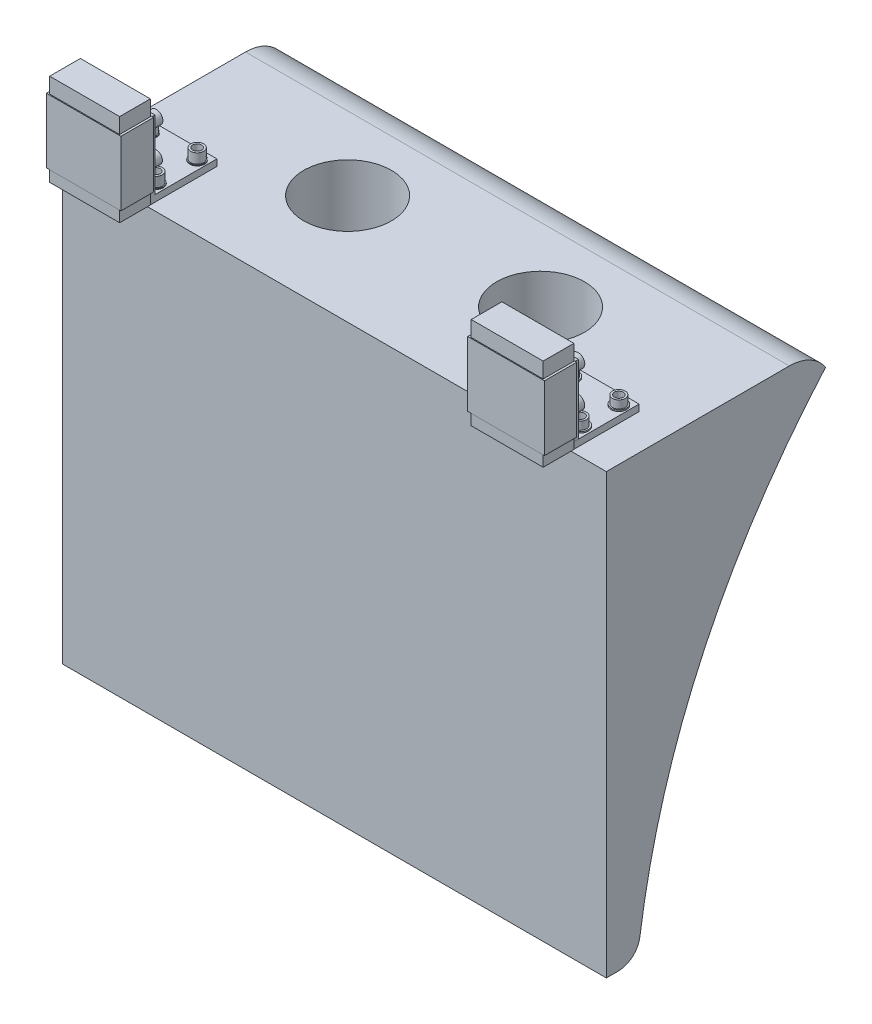
SolidWorks part; units mm, degrees
ref_plane "Front Plane" through (0, 0, 0) normal (0, 0, 1) x (1, 0, 0)
ref_plane "Top Plane" through (0, 0, 0) normal (0, 1, 0) x (1, 0, 0)
ref_plane "Right Plane" through (0, 0, 0) normal (1, 0, 0) x (0, 0, -1)
sketch "Sketch1" plane through (0, 0, 0) normal (1, 0, 0) x (0, 0, -1)
  line L0 (-139.1874, 113.9977) -> (-139.1874, -86.0023)
  line L1 (-139.1874, -86.0023) -> (-125.0344, -86.0023)
  line L4 (-39.1874, 113.9977) -> (-139.1874, 113.9977)
  line L5 (-39.1874, 113.9977) -> (-39.1874, 105.2432)
  spline S2 degree 2 poles (-125.0344, -86.0023) (-112.0669, 22.1606) (-39.1874, 105.2432) knots 0 0 0 1 1 1
  dimension "D1" = 200
  dimension "D2" = 100
extrude "Boss-Extrude1" add sketch "Sketch1" along normal blind 242 and the other way blind 6 contours L5 S2 L1 L0 L4
fillet "Fillet1" radius 10 1 edges at (118, -86.0023, 125.0344)
sketch "Sketch2" plane through (0, 113.9977, 0) normal (0, 1, 0) x (1, 0, 0)
  line L0 (242, -139.1874) -> (-6, -139.1874) construction
  line L1 (242, -39.1874) -> (242, -139.1874) construction
  line L2 (-6, -39.1874) -> (-6, -139.1874) construction
  circle A0 centre (162, -89.1874) radius 20
  circle A1 centre (44, -39.1874) radius 35
  point P10 (143, -89.1874)
  point P11 (0, 0)
  dimension "D5" = 70
  dimension "D6" = 40
  dimension "D1" = 50
  dimension "D2" = 80
  dimension "D3" = 50
  dimension "D4" = 100
extrude "Cut-Extrude2" cut sketch "Sketch2" against normal blind 30 contours A0
sketch "Sketch4" plane through (0, 113.9977, 0) normal (0, 1, 0) x (1, 0, 0)
  line L0 (-6, -39.1874) -> (-6, -139.1874) construction
  line L1 (242, -139.1874) -> (-6, -139.1874) construction
  circle A0 centre (74, -89.1874) radius 20
  dimension "D1" = 40
  dimension "D2" = 80
  dimension "D3" = 50
extrude "Cut-Extrude3" cut sketch "Sketch4" against normal blind 30
fillet "Fillet2" radius 20 1 edges at (118, 113.9977, 39.1874)
sketch "Sketch5" plane through (0, 113.9977, 0) normal (0, 1, 0) x (1, 0, 0)
  line L1 (287.0474, -139.0857) -> (257.0932, -139.0857)
  line L2 (287.0474, -139.0857) -> (287.0474, -108.0353)
  line L3 (287.0474, -108.0353) -> (257.0932, -108.0353)
  line L4 (257.0932, -139.0857) -> (257.0932, -108.0353)
  line L5 (3.1819, -139.2752) -> (32.6867, -139.2752)
  line L6 (3.1819, -139.2752) -> (3.1819, -107.4758)
  line L7 (3.1819, -107.4758) -> (32.6867, -107.4758)
  line L8 (32.6867, -139.2752) -> (32.6867, -107.4758)
extrude "Boss-Extrude2" add sketch "Sketch5" along normal blind 3
sketch "Sketch6" plane through (0, 116.9977, 0) normal (0, 1, 0) x (1, 0, 0)
  circle A0 centre (282.4766, -130.3755) radius 3.7166
  circle A1 centre (261.3092, -130.3442) radius 3.5214
  circle A2 centre (282.925, -113.1792) radius 3.4861
  circle A3 centre (261.0046, -113.1473) radius 3.5318
extrude "Boss-Extrude3" add sketch "Sketch6" along normal blind 0.6 contours A1 | A3 | A2 | A0 region at (261.3092, 116.9977, 130.3442) region at (282.925, 116.9977, 113.1792) region at (261.0046, 116.9977, 113.1473)
sketch "Sketch7" plane through (0, 117.5977, 0) normal (0, 1, 0) x (1, 0, 0)
  circle A0 centre (261.3092, -130.3442) radius 2.7903
  circle A1 centre (261.0046, -113.1473) radius 2.8891
  circle A2 centre (282.4766, -130.3755) radius 2.9455
  circle A3 centre (282.925, -113.1792) radius 2.9236
  circle A4 centre (282.925, -113.1792) radius 2.0236
  circle A5 centre (261.0046, -113.1473) radius 1.9891
  circle A6 centre (261.3092, -130.3442) radius 1.8903
  circle A7 centre (282.4766, -130.3755) radius 2.0455
  dimension "D1" = 0.9
extrude "Boss-Extrude4" add sketch "Sketch7" along normal blind 3.6
sketch "Sketch8" plane through (0, 116.9977, 0) normal (0, 1, 0) x (1, 0, 0)
  circle A0 centre (7.3677, -130.7754) radius 3.5903
  circle A1 centre (28.5717, -131.1234) radius 3.3212
  circle A2 centre (28.6202, -112.4161) radius 3.3684
  circle A3 centre (7.1046, -112.7317) radius 3.3146
extrude "Boss-Extrude5" add sketch "Sketch8" along normal blind 0.4 contours A0 | A3 | A2 | A1 region at (7.3677, 116.9977, 130.7754) region at (28.6202, 116.9977, 112.4161) region at (7.1046, 116.9977, 112.7317)
sketch "Sketch9" plane through (0, 117.3977, 0) normal (0, 1, 0) x (1, 0, 0)
  circle A0 centre (7.0954, -112.6967) radius 2.9562
  circle A1 centre (28.6202, -112.4161) radius 2.9528
  circle A2 centre (7.3677, -130.7754) radius 3.1751
  circle A3 centre (28.5717, -131.1234) radius 2.8914
  circle A4 centre (7.0954, -112.6967) radius 2.0562
  circle A5 centre (28.6202, -112.4161) radius 2.0528
  circle A6 centre (7.3677, -130.7754) radius 2.2751
  circle A7 centre (28.5717, -131.1234) radius 1.9914
  dimension "D1" = 0.9
extrude "Boss-Extrude6" add sketch "Sketch9" along normal blind 4.5
sketch "Sketch11" plane through (0, 116.9977, 0) normal (0, 1, 0) x (1, 0, 0)
  line L0 (287.0474, -139.0857) -> (287.0474, -108.0353) construction
  line L1 (287.0474, -135.7438) -> (257.0932, -135.7438)
  line L2 (287.0474, -135.7438) -> (287.0474, -139.0857)
  line L3 (287.0474, -139.0857) -> (257.0932, -139.0857)
  line L4 (257.0932, -135.7438) -> (257.0932, -139.0857)
  line L5 (32.6867, -139.2752) -> (32.6867, -107.4758) construction
  line L6 (32.6867, -135.7438) -> (3.1819, -135.7438)
  line L7 (32.6867, -135.7438) -> (32.6867, -139.2752)
  line L8 (32.6867, -139.2752) -> (3.1819, -139.2752)
  line L9 (3.1819, -135.7438) -> (3.1819, -139.2752)
extrude "Boss-Extrude7" add sketch "Sketch11" along normal blind 31.5
sketch "Sketch12" plane through (0, 0, 135.7438) normal (0, 0, -1) x (-1, 0, 0)
  circle A0 centre (-282.078, 143.2555) radius 3.5716
  circle A1 centre (-261.9163, 142.919) radius 3.63
  circle A2 centre (-281.9256, 126.8001) radius 3.5382
  circle A3 centre (-261.7812, 126.8367) radius 3.5128
extrude "Boss-Extrude8" add sketch "Sketch12" along normal blind 0.4
sketch "Sketch13" plane through (0, 0, 135.7438) normal (0, 0, -1) x (-1, 0, 0)
  circle A0 centre (-28.4144, 143.1344) radius 3.3554
  circle A1 centre (-28.4527, 127.3354) radius 3.1994
  circle A2 centre (-7.3975, 127.1758) radius 3.1344
  circle A3 centre (-7.6472, 142.9311) radius 3.4439
extrude "Boss-Extrude9" add sketch "Sketch13" along normal blind 0.4 contours A0 | A1 | A2 | A3 region at (28.4144, 143.1344, 135.7438) region at (28.4527, 127.3354, 135.7438) region at (7.3975, 127.1758, 135.7438)
sketch "Sketch14" plane through (0, 0, 135.3438) normal (0, 0, -1) x (-1, 0, 0)
  circle A0 centre (-282.078, 143.2555) radius 2.9987
  circle A1 centre (-261.873, 142.9358) radius 3.1841
  circle A2 centre (-261.7812, 126.8367) radius 2.9866
  circle A3 centre (-281.9256, 126.8001) radius 3.0844
  circle A4 centre (-28.44, 143.1429) radius 2.9722
  circle A5 centre (-7.6472, 142.9311) radius 2.9949
  circle A6 centre (-28.4527, 127.3354) radius 2.7475
  circle A7 centre (-7.3975, 127.1758) radius 2.743
  circle A8 centre (-28.44, 143.1429) radius 2.0722
  circle A9 centre (-7.6472, 142.9311) radius 2.0949
  circle A10 centre (-28.4527, 127.3354) radius 1.8475
  circle A11 centre (-7.3975, 127.1758) radius 1.843
  circle A12 centre (-282.078, 143.2555) radius 2.0987
  circle A13 centre (-261.873, 142.9358) radius 2.2841
  circle A14 centre (-281.9256, 126.8001) radius 2.1844
  circle A15 centre (-261.7812, 126.8367) radius 2.0866
  dimension "D1" = 0.9
extrude "Boss-Extrude10" add sketch "Sketch14" along normal blind 4.5
sketch "Sketch15" plane through (0, 0, 139.0857) normal (0, 0, 1) x (1, 0, 0)
  line L1 (255.5139, 157.1398) -> (288.336, 157.1398)
  line L2 (255.5139, 157.1398) -> (255.5139, 115.1906)
  line L3 (255.5139, 115.1906) -> (288.336, 115.1906)
  line L4 (288.336, 157.1398) -> (288.336, 115.1906)
  line L5 (2.0437, 157.1398) -> (33.9407, 157.1398)
  line L6 (2.0437, 157.1398) -> (2.0437, 115.1906)
  line L7 (2.0437, 115.1906) -> (33.9407, 115.1906)
  line L8 (33.9407, 157.1398) -> (33.9407, 115.1906)
extrude "Boss-Extrude11" add sketch "Sketch15" along normal blind 14
sketch "Sketch17" plane through (33.9407, 0, 0) normal (1, 0, 0) x (0, 0, -1)
  line L1 (-153.4979, 150.0543) -> (-138.5796, 150.0543)
  line L2 (-153.4979, 150.0543) -> (-153.4979, 120.5867)
  line L3 (-153.4979, 120.5867) -> (-138.5796, 120.5867)
  line L4 (-138.5796, 150.0543) -> (-138.5796, 120.5867)
extrude "Boss-Extrude12" add sketch "Sketch17" against normal blind 33 and the other way blind 1
sketch "Sketch18" plane through (288.336, 0, 0) normal (1, 0, 0) x (0, 0, -1)
  line L1 (-153.4979, 150.0543) -> (-138.8367, 150.0543)
  line L2 (-153.4979, 150.0543) -> (-153.4979, 120.4908)
  line L3 (-153.4979, 120.4908) -> (-138.8367, 120.4908)
  line L4 (-138.8367, 150.0543) -> (-138.8367, 120.4908)
extrude "Boss-Extrude13" add sketch "Sketch18" along normal blind 1 and the other way blind 34
move or copy body "Body-Move/Copy1" bodies to move or copy 122 119 127 130 133 108 123 126 117 128 131 120 129 134 copy no translate (-46.4807, 0, 0)
move or copy body "Body-Move/Copy2" bodies to move or copy 112 121 124 107 132 125 copy no translate (-46.4953, 0, 0)
move or copy body "Body-Move/Copy3" bodies to move or copy 154 145 138 141 135 152 150 139 146 148 142 143 144 136 137 140 153 149 151 147 copy no translate (-14.7702, 0, 0)
